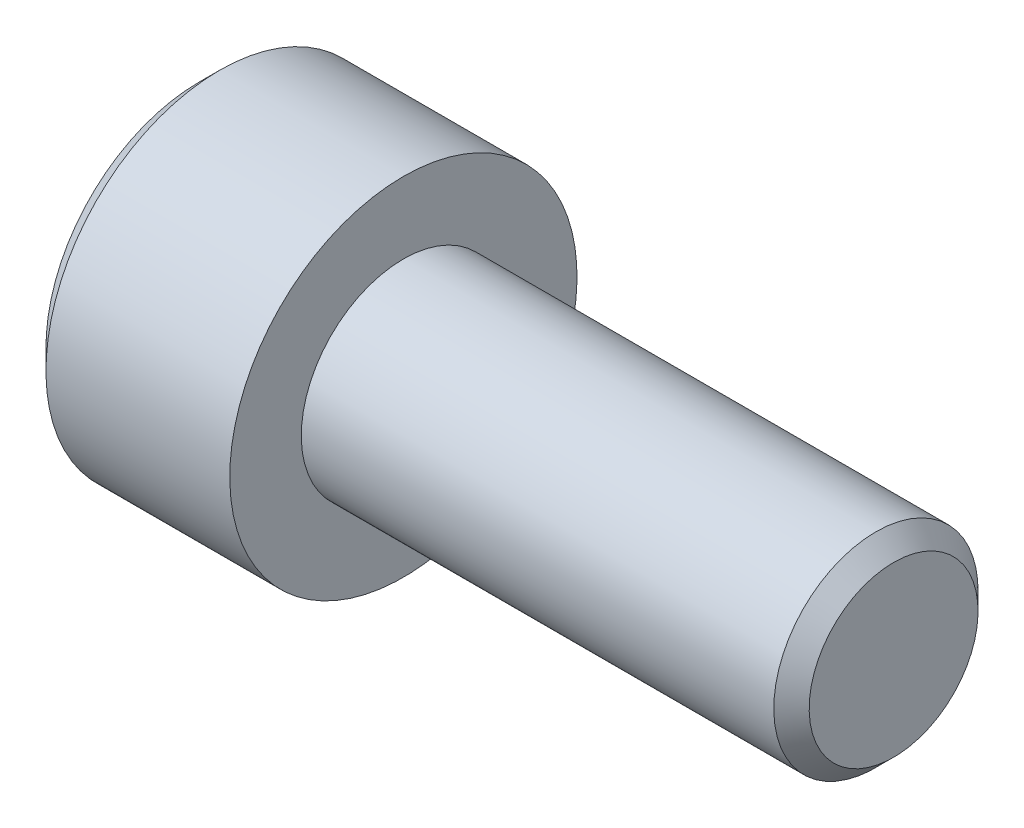
SolidWorks part; units mm, degrees
ref_plane "Front Plane" through (0, 0, 0) normal (0, 0, 1) x (1, 0, 0)
ref_plane "Top Plane" through (0, 0, 0) normal (0, 1, 0) x (1, 0, 0)
ref_plane "Right Plane" through (0, 0, 0) normal (1, 0, 0) x (0, 0, -1)
ref_axis "Axis_X" through (-5.85, 0, 0) along (1, 0, 0)
ref_axis "Axis_Y" through (0, 4.675, 0) along (0, -1, 0)
ref_axis "Axis_Z" through (0, 0, -4.675) along (0, 0, 1)
sketch "Sketch1" plane through (0, 0, 0) normal (0, 0, 1) x (1, 0, 0)
  line L0 (-4.1583, 0) -> (12, 0) construction
  line L1 (0, 2.5) -> (0, 4.25)
  line L2 (-5, 0) -> (-5, 3.75)
  line L3 (0, 2.5) -> (11.567, 2.5)
  line L4 (11.567, 2.5) -> (12, 2.067)
  line L5 (12, 2.067) -> (12, 0)
  line L6 (12, 0) -> (-5, 0)
  line L7 (-4.5, 4.25) -> (0, 4.25)
  line L8 (11.567, -2.5) -> (12, -2.067) construction
  line L9 (4.675, 0) -> (-4.675, 0) construction
  line L10 (-5, 3.75) -> (-4.5, 4.25)
  line L11 (-5, -3.75) -> (-4.5, -4.25) construction
  line L12 (0, -4.675) -> (0, 4.675) construction
  dimension "FIX_1" = 45
  dimension "M" = 5
  dimension "ATD_1" = 4.134
  dimension "L" = 12
  dimension "E" = 5
  dimension "A" = 8.5
revolve "Revolve1" add sketch "Sketch1" angle 360 about L6
sketch "Sketch2" plane through (-5, 0, 0) normal (-1, 0, 0) x (0, 0, 1)
  line L0 (0, -4.675) -> (0, 4.675) construction
  line L1 (0, 2.3094) -> (-2, 1.1547)
  line L2 (-2, 1.1547) -> (-2, -1.1547)
  line L3 (-2, -1.1547) -> (0, -2.3094)
  line L4 (0, -2.3094) -> (2, -1.1547)
  line L5 (2, -1.1547) -> (2, 1.1547)
  line L6 (2, 1.1547) -> (0, 2.3094)
  circle A0 centre (0, 0) radius 2 construction
  dimension "B" = 4
extrude "Cut-Extrude1" cut sketch "Sketch2" against normal blind 2.5
equation "\"Factor\"= 1.082532"
equation "\"Pitch\"= IIF ( \"M\" = 30 , 3.5 , IIF ( \"M\" = 24 , 3 , IIF ( \"M\" = 20 , 2.5 , IIF ( \"M\" = 16 , 2 , IIF ( \"M\" = 14 , 2 , IIF ( \"M\" = 12 , 1.75 , IIF ( \"M\" = 10 , 1.5 , IIF ( \"M\" = 8 , 1.25 , IIF ( \"M\" = 6 , 1 , IIF ( \"M\" = 5 , 0.8 , IIF ( \"M\" = 4 , 0.7 , IIF ( \"M\" = 3 , 0.5 , IIF ( \"M\" = 2.5 , 0.45 , 0.4 ) ) ) ) ) ) ) ) ) ) ) ) )"
equation "\"ATD_1\"= round ( \"M\" - \"Factor\" * \"Pitch\" , 3 )"
equation "\"L_s\"= IIF ( ( \"M\" = 12 and \"L\" > 50 ) , 36 , IIF ( ( \"M\" = 12 and \"L\" = < 50 ) , \"L\" , IIF ( ( \"M\" = 10 and \"L\" > 40 ) , 32 , IIF ( ( \"M\" = 10 and \"L\" = < 40 ) , \"L\" , IIF ( ( \"M\" = 8 and \"L\" > 35 ) , 28 , IIF ( ( \"M\" = 8 and \"L\" = < 35 ) , \"L\" , IIF ( ( \"M\" = 6 and \"L\" > 30 ) , 24 , IIF ( ( \"M\" = 6 and \"L\" = < 30 ) , \"L\" , IIF ( ( \"M\" = 5 and \"L\" > 25 ) , 22 , IIF ( ( \"M\" = 5 and \"L\" = < 25 ) , \"L\" , IIF ( ( \"M\" = 4 and \"L\" > 25 ) , 20 , IIF ( ( \"M\" = 4 and \"L\" = < 25 ) , \"L\" , IIF ( ( \"M\" = 3 and \"L\" > 20 ) , 18 , \"L\" ) ) ) ) ) ) ) ) ) ) ) ) )"
equation "\"E\"= \"M\""
equation "\"A\"= IIF ( \"M\" = 12 , 18 , IIF ( \"M\" = 10 , 16 , IIF ( \"M\" = 8 , 13 , IIF ( \"M\" = 6 , 10 , IIF ( \"M\" = 5 , 8.5 , IIF ( \"M\" = 4 , 7 , 5.5 ) ) ) ) ) )"
equation "\"B\"= IIF ( \"M\" = 12 , 10 , IIF ( \"M\" = 10 , 8 , IIF ( \"M\" = 8 , 6 , IIF ( \"M\" = 6 , 5 , IIF ( \"M\" = 5 , 4 , IIF ( \"M\" = 4 , 3 , 2.5 ) ) ) ) ) )"
equation "\"KSS_1\"= \"M\" / 10"
equation "\"KSS_2\"= \"M\" / 2"
